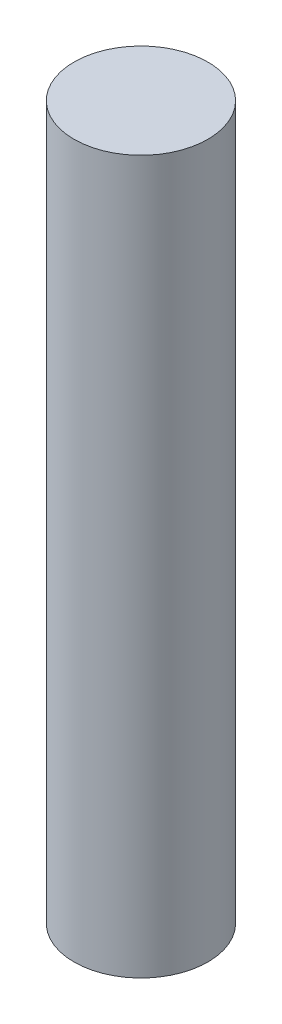
SolidWorks part; units mm, degrees
ref_plane "Front Plane" through (0, 0, 0) normal (0, 0, 1) x (1, 0, 0)
ref_plane "Top Plane" through (0, 0, 0) normal (0, 1, 0) x (1, 0, 0)
ref_plane "Right Plane" through (0, 0, 0) normal (1, 0, 0) x (0, 0, -1)
sketch "Sketch1" plane through (0, 0, 0) normal (0, 1, 0) x (1, 0, 0)
  circle A0 centre (0, 0) radius 3.175
  dimension "D1" = 6.35
sketch "Sketch2" plane through (0, 0, 0) normal (1, 0, 0) x (0, 0, -1)
  line L0 (0, 0) -> (0, 33.795)
  circle A0 centre (0, 0) radius 33.795 construction
extrude "Boss-Extrude1" add sketch "Sketch1" along normal up to vertex (33.795 mm away) contours A0 up to point (0, 33.795, 0)
